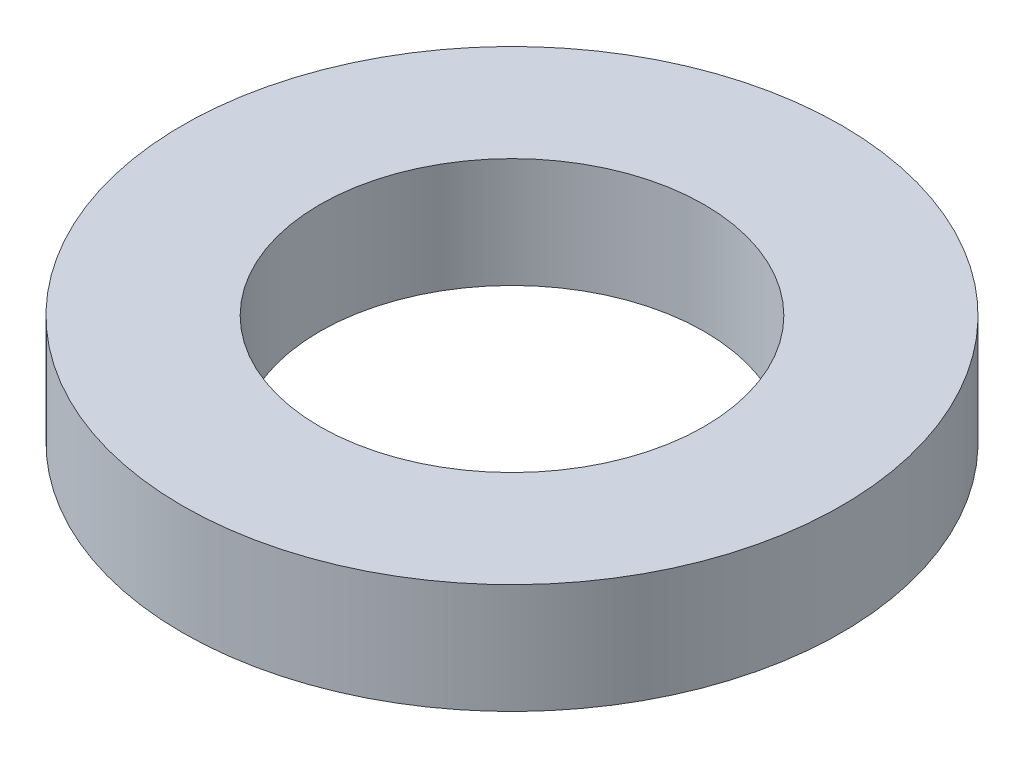
SolidWorks part; units mm, degrees
ref_plane "Front Plane" through (0, 0, 0) normal (0, 0, 1) x (1, 0, 0)
ref_plane "Top Plane" through (0, 0, 0) normal (0, 1, 0) x (1, 0, 0)
ref_plane "Right Plane" through (0, 0, 0) normal (1, 0, 0) x (0, 0, -1)
sketch "Sketch1" plane through (0, 0, 0) normal (0, 1, 0) x (1, 0, 0)
  circle A0 centre (0, 0) radius 60
  dimension "FLANGE_OD" = 120
extrude "Boss-Extrude1" add sketch "Sketch1" along normal blind 20
sketch "Sketch2" plane through (0, 0, 0) normal (0, 1, 0) x (1, 0, 0)
  circle A0 centre (0, 0) radius 35
  dimension "BORE_D" = 70
extrude "Cut-Extrude1" cut sketch "Sketch2" along normal through all
sketch "Sketch3" plane through (0, 20, 0) normal (0, 1, 0) x (1, 0, 0)
  circle A0 centre (0, 0) radius 26.7899 construction
  circle A1 centre (-26.7899, 0) radius 2.81
  dimension "BOLT_D" = 5.62
  dimension "BOLT_PCD" = 53.5798
extrude "Cut-Extrude2" cut sketch "Sketch3" against normal blind 19.2524 rebuild error yes
pattern_circular "CirPattern1" count 6 over 360 rebuild error yes
